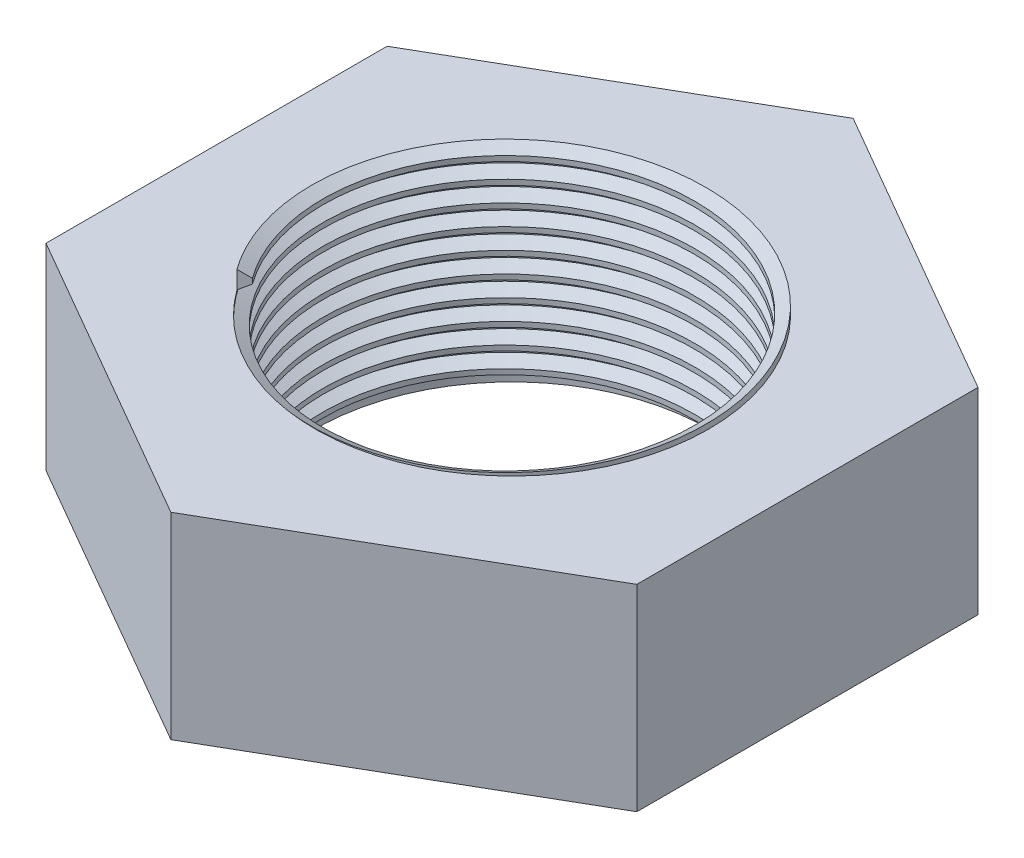
SolidWorks part; units mm, degrees
ref_plane "Front" through (0, 0, 0) normal (0, 0, 1) x (1, 0, 0)
ref_plane "Top" through (0, 0, 0) normal (0, 1, 0) x (1, 0, 0)
ref_plane "Right" through (0, 0, 0) normal (1, 0, 0) x (0, 0, -1)
sketch "Sketch1" plane through (0, 0, 0) normal (0, 1, 0) x (1, 0, 0)
  line L1 (0, 8.7988) -> (-7.62, 4.3994)
  line L2 (-7.62, 4.3994) -> (-7.62, -4.3994)
  line L3 (-7.62, -4.3994) -> (0, -8.7988)
  line L4 (0, -8.7988) -> (7.62, -4.3994)
  line L5 (7.62, -4.3994) -> (7.62, 4.3994)
  line L6 (7.62, 4.3994) -> (0, 8.7988)
  circle A0 centre (0, 0) radius 7.62 construction
  circle A1 centre (0, 0) radius 5.08
  dimension "D2" = 10.16
  dimension "D1" = 7.62
extrude "Boss-Extrude1" add sketch "Sketch1" along normal blind 5.08
thread "Thread1" pitch 0.5292 method extrude profile "Thread Profile1" start angle 0, offset 0, length 0, pitch 0.5292, diameter 10.16
ref_plane "Plane1" through (5.08, 0, 0) normal (0, 0, 1) x (1, 0, 0)
sketch "Thread Profile1" plane through (5.08, 0, 0) normal (0, 0, 1) x (1, 0, 0)
  line L0 (0, 0) -> (0, 0.5292) construction
  line L11 (0, 0) -> (0, 0.463)
  line L12 (0, 0.463) -> (-0.2864, 0.2977)
  line L13 (-0.2864, 0.2977) -> (-0.2864, 0.1654)
  line L15 (-0.2864, 0.1654) -> (0, 0)
  line L17 (-0.2864, 0.2315) -> (0, 0.2315) construction
  point P2 (0, 0)
  dimension "Pitch" = 0.5292
  dimension "Profile_Angle" = 60
  dimension "Profile_Land" = 0.1323
  dimension "Profile_Height" = 0.2864
